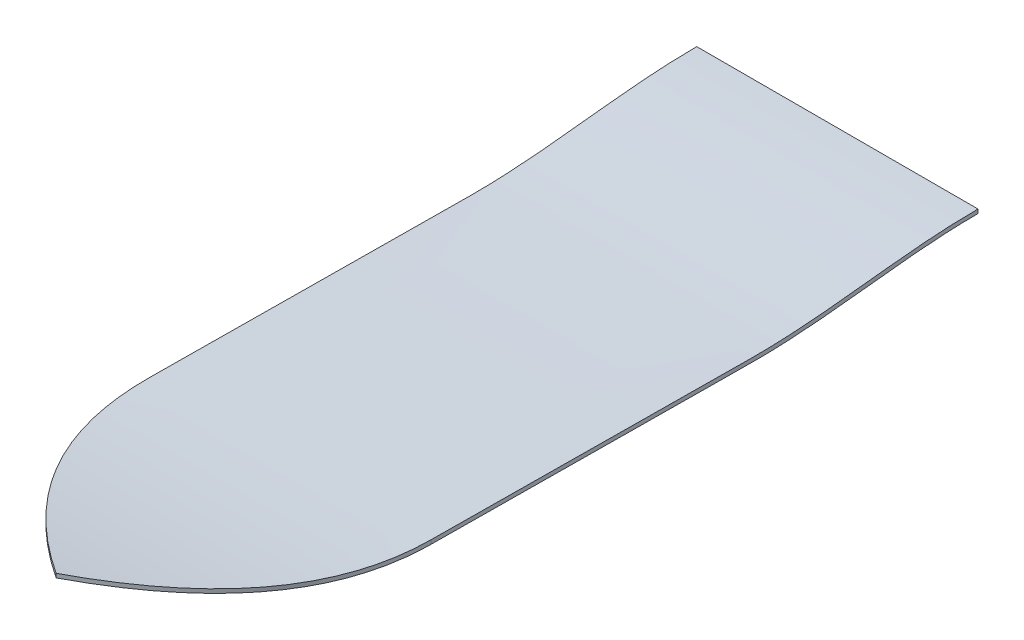
SolidWorks part; units mm, degrees
ref_plane "Front Plane" through (0, 0, 0) normal (0, 0, 1) x (1, 0, 0)
ref_plane "Top Plane" through (0, 0, 0) normal (0, 1, 0) x (1, 0, 0)
ref_plane "Right Plane" through (0, 0, 0) normal (1, 0, 0) x (0, 0, -1)
sketch "Sketch1" plane through (0, 0, 0) normal (1, 0, 0) x (0, 0, -1)
  line L0 (-2543.9836, 91.5006) -> (-2547.9286, 66.4088)
  line L1 (2455.2444, 60.7522) -> (2455.2444, 35.3522)
  spline S0 degree 3 poles (-2543.9836, 91.5006) (-2312.0356, 55.0337) (-1972.0739, 16.2277) (-1494.6551, -12.3936) (-1247.39, -19.826) (-1100.6392, -21.6769) (-1073.2398, -21.9434) (-1052.6732, -22.1295) (-953.2815, -23.04) (-775.0611, -24.6719) (-500.8746, -27.1814) (-199.2695, -29.942) (129.7543, -32.9535) (431.3594, -35.714) (705.546, -38.2237) (878.6277, -39.8094) (972.8766, -40.6694) (986.5876, -40.7965) (1005.396, -40.927) (1088.6934, -41.0221) (1233.8008, -36.7266) (1715.2391, -3.0184) (2093.6202, 60.7522) (2455.2444, 60.7522) knots 0 0 0 0 0.15625 0.21875 0.289062 0.300781 0.302734 0.304688 0.3125 0.359375 0.40625 0.46875 0.53125 0.59375 0.640625 0.6875 0.692383 0.694336 0.695312 0.703125 0.742188 0.78125 1 1 1 1
  spline S1 degree 1 poles (-2547.9286, 66.4088) (2455.2444, 35.3522) knots 0 0 1 1 construction
  spline S2 degree 3 poles (-2547.9286, 66.4088) (-2542.1057, 65.4933) (-2530.4663, 63.6765) (-2507.1126, 60.0835) (-2477.826, 55.6758) (-2442.5167, 50.5179) (-2395.2221, 43.8166) (-2335.6974, 35.7694) (-2263.6182, 26.64) (-2190.8892, 18.0375) (-2093.0508, 7.2702) (-1969.1282, -4.8719) (-1817.8215, -17.3355) (-1663.9148, -27.693) (-1507.4084, -35.945) (-1374.8182, -41.0667) (-1267.4485, -44.1136) (-1186.264, -45.8681) (-1118.0913, -46.9067) (-1063.1743, -47.4407) (-1008.3587, -47.9328) (-939.8022, -48.5656) (-830.1322, -49.5679) (-693.0371, -50.8239) (-528.5258, -52.3293) (-364.0138, -53.8352) (-199.5019, -55.3409) (-34.99, -56.8467) (129.5218, -58.3524) (294.0337, -59.8582) (458.5456, -61.3639) (595.6389, -62.6187) (705.3137, -63.623) (787.5702, -64.3763) (856.1169, -65.0039) (910.9542, -65.5048) (945.2262, -65.819) (969.2185, -66.0358) (982.9213, -66.1657) (996.7244, -66.2745) (1013.8622, -66.3363) (1041.1699, -66.3003) (1075.0353, -65.9984) (1128.694, -65.0008) (1194.8159, -62.8415) (1272.7896, -58.9668) (1349.5369, -53.9835) (1450.4277, -46.0944) (1574.212, -34.3366) (1720.2143, -18.5886) (1864.8758, -2.5902) (1985.3166, 9.8011) (2082.2125, 18.4647) (2155.3096, 24.1673) (2228.9862, 28.9047) (2290.9949, 31.9064) (2341.0474, 33.6554) (2378.827, 34.6196) (2410.5334, 35.1159) (2436.0269, 35.3179) (2448.8444, 35.3522) (2455.2444, 35.3522) knots 0 0 0 0 0.003906 0.007812 0.015625 0.023438 0.03125 0.046875 0.0625 0.078125 0.09375 0.125 0.15625 0.1875 0.21875 0.25 0.265625 0.28125 0.296875 0.304688 0.3125 0.328125 0.34375 0.375 0.40625 0.4375 0.46875 0.5 0.53125 0.5625 0.59375 0.625 0.640625 0.65625 0.671875 0.679688 0.6875 0.691406 0.693359 0.695312 0.699219 0.703125 0.710938 0.71875 0.734375 0.75 0.765625 0.78125 0.8125 0.84375 0.875 0.90625 0.921875 0.9375 0.953125 0.96875 0.976562 0.984375 0.992188 0.996094 1 1 1 1
  dimension "D1" = 25.4
extrude "Boss-Extrude1" add sketch "Sketch1" along normal blind 1524 and the other way blind 1524
sketch "Sketch3" plane through (0, 0, 0) normal (0, 1, 0) x (1, 0, 0)
  line L0 (-899.9962, 2455.2444) -> (900.0038, 2455.2444)
  line L1 (-899.9962, 2455.2444) -> (-899.9962, -1044.7556)
  line L2 (900.0038, 2455.2444) -> (900.0038, -1044.7556)
  line L3 (-1524, 2455.2444) -> (1524, 2455.2444) construction
  line L4 (-1976.5237, 2801.7222) -> (3754.9336, 2801.7222)
  line L5 (-1976.5237, 2801.7222) -> (-1976.5237, -4542.2553)
  line L6 (-1976.5237, -4542.2553) -> (3754.9336, -4542.2553)
  line L7 (3754.9336, 2801.7222) -> (3754.9336, -4542.2553)
  line L8 (-1524, 2455.2444) -> (1524, 2455.2444)
  line L9 (127.0211, 2455.2419) -> (0.0038, 2455.2419) construction
  line L10 (127.0211, 2455.2419) -> (0.0038, 2455.2419)
  spline S0 degree 2 poles (-899.9962, -1044.7556) (-899.9962, -1919.3942) (0.0038, -2544.7556) knots 0 0 0 1 1 1
  spline S1 degree 2 poles (900.0038, -1044.7556) (900.0038, -1919.3942) (0.0038, -2544.7556) knots 0 0 0 1 1 1
  point P13 (0, 0)
  point P14 (0, 0)
  point P15 (-899.9962, -1044.7556)
  point P16 (247.4439, -2544.7556)
  dimension "D1" = 1800
  dimension "D2" = 900
  dimension "D3" = 5000
  dimension "D4" = 1500
  dimension "900" = 900
extrude "Cut-Extrude1" cut sketch "Sketch3" against normal through all both and the other way through all contours L7 L4 L5 L6 L2 S1 S0 L1 L0 region at (1103.5236, 0, 1121.3779)
